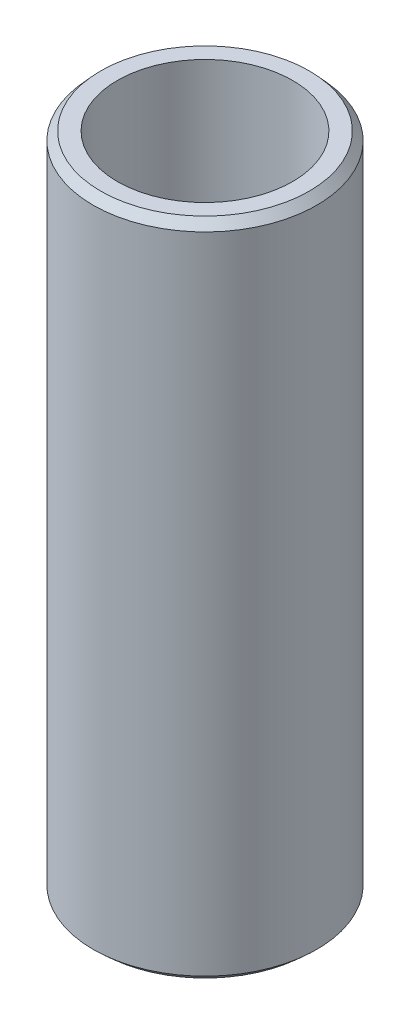
SolidWorks part; units mm, degrees
ref_plane "Front Plane" through (0, 0, 0) normal (0, 0, 1) x (1, 0, 0)
ref_plane "Top Plane" through (0, 0, 0) normal (0, 1, 0) x (1, 0, 0)
ref_plane "Right Plane" through (0, 0, 0) normal (1, 0, 0) x (0, 0, -1)
sketch "Sketch1" plane through (0, 0, 0) normal (0, 1, 0) x (1, 0, 0)
  circle A0 centre (0, 0) radius 37.5
  dimension "SHAFT_OD" = 75
extrude "Boss-Extrude1" add sketch "Sketch1" along normal blind 221.4805
sketch "Sketch2" plane through (0, 0, 0) normal (0, 1, 0) x (1, 0, 0)
  circle A0 centre (0, 0) radius 29.3967
  dimension "BORE_D" = 58.7934
extrude "Cut-Extrude1" cut sketch "Sketch2" along normal through all
chamfer "Chamfer1" distance 2.8107 angle 42.128 2 edges at (0, 221.4805, 37.5) (0, 0, 37.5) first distance on face at (0, 221.4805, 37.5) first distance on face at (0, 0, 29.3967)
